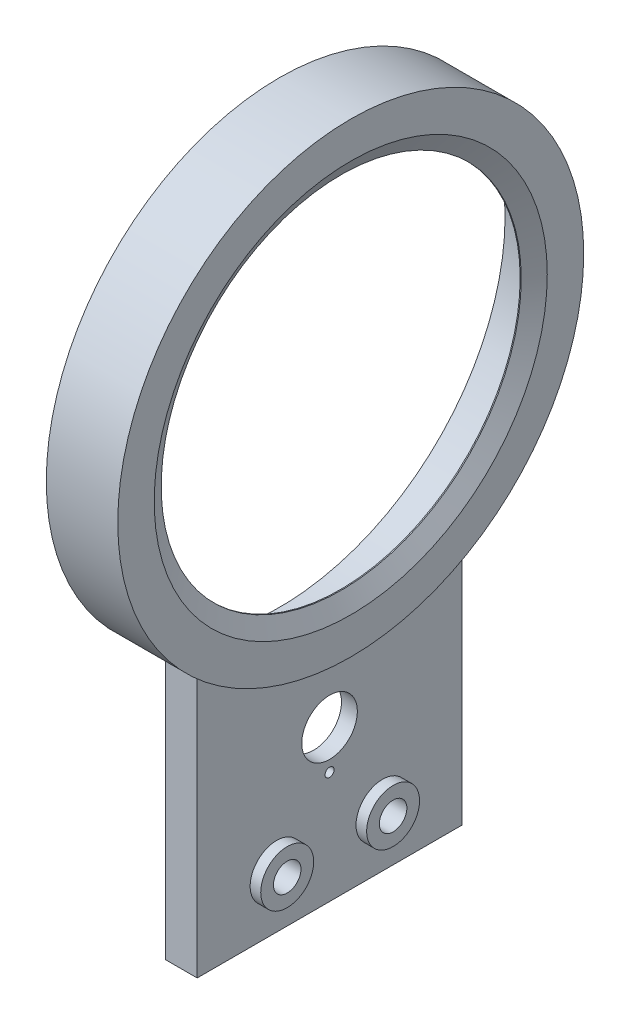
SolidWorks part; units mm, degrees
ref_plane "Front Plane" through (0, 0, 0) normal (0, 0, 1) x (1, 0, 0)
ref_plane "Top Plane" through (0, 0, 0) normal (0, 1, 0) x (1, 0, 0)
ref_plane "Right Plane" through (0, 0, 0) normal (1, 0, 0) x (0, 0, -1)
sketch "Sketch1" plane through (0, 0, 0) normal (1, 0, 0) x (0, 0, -1)
  line L0 (0, -6) -> (0, 6) construction
  line L1 (-7.5, 0) -> (7.5, 0) construction
  circle A0 centre (0, 0) radius 42.65
  circle A1 centre (0, 0) radius 44
  circle A2 centre (0, 0) radius 2.1 construction
  circle A3 centre (0, 6) radius 1.5 construction
  circle A4 centre (7.5, 0) radius 1.5 construction
  circle A5 centre (0, -6) radius 1.5 construction
  circle A6 centre (-7.5, 0) radius 1.5 construction
  circle A7 centre (0, 0) radius 34
  point P7 (0, 0)
  point P11 (0, 0)
  dimension "D1" = 88
  dimension "D2" = 85.3
  dimension "D3" = 4.2
  dimension "D6" = 3
  dimension "D7" = 3
  dimension "D8" = 3
  dimension "D9" = 3
  dimension "D10" = 68
  dimension "D4" = 15
  dimension "D5" = 12
extrude "Boss-Extrude1" add sketch "Sketch1" against normal blind 11.5 contours A1 A0 region at (0, 0, 42.7555)
extrude "Boss-Extrude2" add sketch "Sketch1<2>" along normal blind 2 contours A0 | A1 A0 region at (0, 0, 41.4437) region at (0, 0, 42.7555)
sketch "Sketch1<2>" plane through (0, 0, 0) normal (1, 0, 0) x (0, 0, -1) same geometry as "Sketch1"
ref_plane "Plane1" through (-2, 0, 0) normal (1, 0, 0) x (0, 0, -1)
sketch "Sketch5" plane through (-2, 0, 0) normal (1, 0, 0) x (0, 0, -1)
  line L0 (0, 0) -> (0, -78.2719) construction
  line L1 (-25, -44) -> (25, -44) construction
  line L2 (-25, -86) -> (25, -86)
  line L3 (-25, -86) -> (-25, -36.2077)
  line L5 (25, -86) -> (25, -36.2077)
  circle A0 centre (0, 0) radius 44 construction
  circle A2 centre (0, 0) radius 44
  circle A5 centre (0, 0) radius 44
  point P12 (0, -44)
  dimension "D1" = 50
  dimension "D2" = 25
  dimension "D3" = 42
  dimension "D4" = 0
extrude "Boss-Extrude3" add sketch "Sketch5" against normal blind 6 contours L2 L5 L3 | L5 L2 L3 region at (-2, -63.6922, 0)
sketch "Sketch7" plane through (0, 0, 0) normal (-1, 0, 0) x (0, 0, 1)
  circle A0 centre (0, 0) radius 42.65
  circle A1 centre (0, 0) radius 39.5
  dimension "D1" = 85.3
  dimension "D2" = 79
extrude "Boss-Extrude4" add sketch "Sketch7" along normal blind 1
sketch "Sketch8" plane through (-2, 0, 0) normal (1, 0, 0) x (0, 0, -1)
  line L0 (0, 0) -> (0, -57.5) construction
  line L1 (0, -57.5) -> (0, -64.86) construction
  line L2 (-25, -86) -> (25, -86) construction
  line L3 (-25, -86) -> (-25, -36.2077) construction
  line L4 (25, -86) -> (25, -36.2077) construction
  circle A0 centre (0, -57.5) radius 5.25
  circle A1 centre (0, -64.86) radius 0.85
  circle A2 centre (-10, -76) radius 2.6
  circle A3 centre (10, -76) radius 2.6
  dimension "D2" = 10.5
  dimension "D4" = 1.7
  dimension "D7" = 5.2
  dimension "D10" = 5.2
  dimension "D1" = 57.5
  dimension "D3" = 7.36
  dimension "D5" = 10
  dimension "D6" = 15
  dimension "D8" = 15
  dimension "D9" = 10
extrude "Cut-Extrude3" cut sketch "Sketch8" against normal blind 10
sketch "Sketch9" plane through (-8, 0, 0) normal (-1, 0, 0) x (0, 0, 1)
  circle A0 centre (0, -57.5) radius 12.5
  dimension "D1" = 25
extrude "Cut-Extrude4" cut sketch "Sketch9" against normal blind 3
chamfer "Chamfer1" distance 1.8 angle 60 1 edges at (2, 0, -34) first distance on face at (2, 0, -34)
sketch "Sketch11" plane through (-2, 0, 0) normal (-1, 0, 0) x (0, 0, 1)
  circle A0 centre (-10, -76) radius 5
  circle A1 centre (10, -76) radius 5
  circle A2 centre (-10, -76) radius 2.6
  circle A3 centre (10, -76) radius 2.6
  dimension "D1" = 5.2
  dimension "D2" = 5.2
  dimension "D3" = 10
  dimension "D4" = 10
extrude "Boss-Extrude5" add sketch "Sketch11" against normal blind 2
sketch "Sketch10" plane through (-2, 0, 0) normal (1, 0, 0) x (0, 0, -1)
  line L0 (-25, -86) -> (25, -86) construction
  line L1 (-28, -87.9871) -> (28, -87.9871)
  line L2 (-28, -87.9871) -> (-28, -44)
  line L3 (-28, -44) -> (28, -44)
  line L4 (28, -87.9871) -> (28, -44)
  line L6 (-54.3493, 51.4543) -> (51.6324, 51.4543)
  line L7 (-54.3493, 51.4543) -> (-54.3493, -95.2896)
  line L8 (-54.3493, -95.2896) -> (51.6324, -95.2896)
  line L9 (51.6324, 51.4543) -> (51.6324, -95.2896)
  circle A0 centre (0, 0) radius 44 construction
  point P6 (0, -86)
  point P7 (0, -87.9871)
  dimension "D1" = 56
extrude "Cut-Extrude5" [suppressed] cut sketch "Sketch10" against normal through all both and the other way through all
sketch "Sketch12" [suppressed] plane through (-2, 0, 0) normal (1, 0, 0) x (0, 0, -1)
  line L0 (-25, -36.2077) -> (-25, -86) construction
  line L1 (-25, -86) -> (25, -86) construction
  line L2 (25, -86) -> (25, -36.2077) construction
  line L3 (-25, -36.2077) -> (-25, -86)
  line L4 (-25, -86) -> (25, -86)
  line L5 (25, -86) -> (25, -36.2077)
  arc A0 (-25, -36.2077) -> (25, -36.2077) centre (0, 0) ccw construction
  circle A1 centre (0, 0) radius 44 construction
  arc A2 (-25, -36.2077) -> (25, -36.2077) centre (0, 0) ccw
  circle A3 centre (0, 0) radius 44
equation "\"D2@Sketch5\"=\"D1@Sketch5\"/2"
